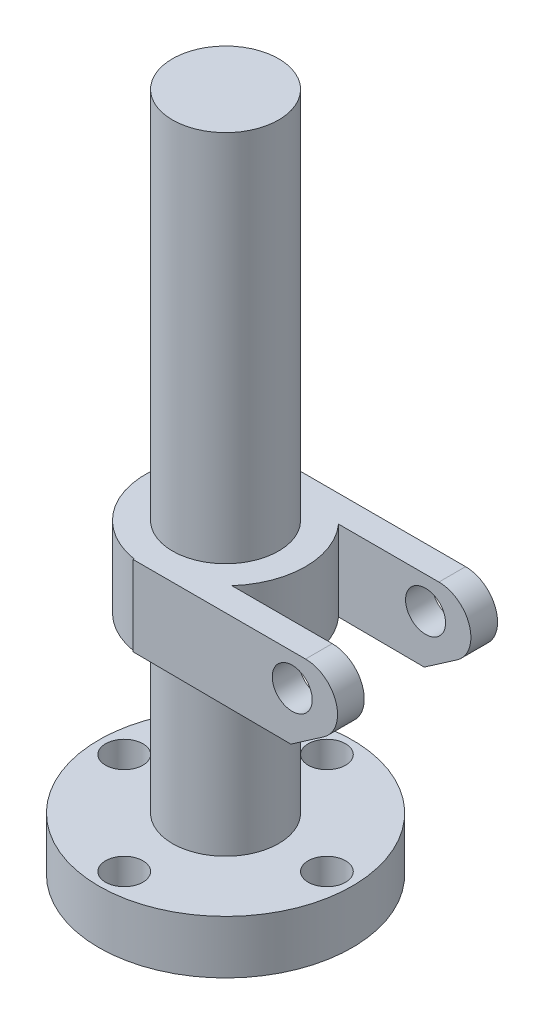
SolidWorks part; units mm, degrees
ref_plane "Front Plane" through (0, 0, 0) normal (0, 0, 1) x (1, 0, 0)
ref_plane "Top Plane" through (0, 0, 0) normal (0, 1, 0) x (1, 0, 0)
ref_plane "Right Plane" through (0, 0, 0) normal (1, 0, 0) x (0, 0, -1)
sketch "Sketch1" plane through (0, 0, 0) normal (0, 1, 0) x (1, 0, 0)
  circle A0 centre (0, 0) radius 47.5
  dimension "D1" = 95
extrude "Boss-Extrude1" add sketch "Sketch1" along normal blind 20
sketch "Sketch2" plane through (0, 20, 0) normal (0, 1, 0) x (1, 0, 0)
  circle A0 centre (0, 0) radius 19.9
  dimension "D1" = 39.8
extrude "Boss-Extrude2" add sketch "Sketch2" along normal blind 65
sketch "Sketch3" plane through (0, 85, 0) normal (0, 1, 0) x (1, 0, 0)
  circle A0 centre (0, 0) radius 30
  dimension "D1" = 60
extrude "Boss-Extrude3" add sketch "Sketch3" along normal blind 30
sketch "Sketch4" plane through (0, 115, 0) normal (0, 1, 0) x (1, 0, 0)
  circle A0 centre (0, 0) radius 19.9
  dimension "D1" = 39.8
extrude "Boss-Extrude4" add sketch "Sketch4" along normal blind 140
sketch "Sketch5" plane through (0, 0, 0) normal (0, 0, 1) x (1, 0, 0)
  line L0 (-4.6849, 115) -> (60, 115)
  line L1 (30, 115) -> (-30, 115) construction
  line L3 (66.8202, 93.1265) -> (54.4856, 84.6063)
  line L4 (54.4856, 84.6063) -> (-4.6849, 85)
  line L5 (-30, 85) -> (30, 85) construction
  line L6 (-4.6849, 85) -> (-4.6849, 115)
  arc A0 (66.8202, 93.1265) -> (60, 115) centre (60, 103) ccw
  dimension "D1" = 24
  dimension "D2" = 60
extrude "Boss-Extrude5" add sketch "Sketch5" along normal blind 30 and the other way blind 30
sketch "Sketch6" plane through (0, 115, 0) normal (0, 1, 0) x (1, 0, 0)
  line L0 (85.6132, 20) -> (85.6132, -20)
  line L1 (85.6132, -20) -> (22.3607, -20)
  line L3 (22.3607, 20) -> (85.6132, 20)
  line L4 (60, 30) -> (-4.6849, 30) construction
  line L5 (60, -30) -> (-4.6849, -30) construction
  arc A0 (22.3607, -20) -> (22.3607, 20) centre (0, 0) ccw
  dimension "D1" = 60
  dimension "D2" = 10
  dimension "D3" = 10
extrude "Cut-Extrude1" cut sketch "Sketch6" against normal blind 40
sketch "Sketch7" plane through (0, 0, 30) normal (0, 0, 1) x (1, 0, 0)
  line L0 (60, 115) -> (-4.6849, 115) construction
  circle A0 centre (55, 103) radius 7.5
  dimension "D1" = 15
  dimension "D2" = 12
  dimension "D3" = 55
extrude "Cut-Extrude2" cut sketch "Sketch7" against normal through all
sketch "Sketch8" plane through (0, 0, 0) normal (0, -1, 0) x (1, 0, 0)
  circle A0 centre (0, 0) radius 20
  dimension "D1" = 40
extrude "Cut-Extrude3" cut sketch "Sketch8" against normal blind 15
sketch "Sketch9" plane through (0, 20, 0) normal (0, 1, 0) x (1, 0, 0)
  circle A0 centre (0, 0) radius 38 construction
  point P0 (0, 38)
  point P5 (0, 0)
  point P6 (0, 0)
  dimension "D1" = 76
sketch "Sketch11" plane through (0, 20, 0) normal (0, 1, 0) x (1, 0, 0)
  point P0 (0, 38)
sketch "Sketch13" plane through (0, 20, 0) normal (0, 1, 0) x (1, 0, 0)
sketch "Sketch15" plane through (0, 20, 0) normal (0, 1, 0) x (1, 0, 0)
  point P0 (0, 38)
hole_wizard "CBORE for M5 Hex Head Bolt3" positions "Sketch15" profile "Sketch14" counterbore size "M5" standard "ISO" end condition through all
sketch "Sketch14" plane through (0, 20, -38) normal (1, 0, 0) x (0, 0, 1)
  line L0 (0, 0) -> (0, 20)
  line L1 (0, 20) -> (5, 20)
  line L3 (5, 20) -> (5, 10)
  line L4 (5, 10) -> (7, 10)
  line L5 (7, 10) -> (7, 0)
  line L7 (7, 0) -> (0, 0)
  line L11 (0, -6.35) -> (0, 107.95) construction
  dimension "Thru Hole Dia." = 10
  dimension "Thru Hole Depth" = 20
  dimension "C'Bore Dia." = 14
  dimension "C'Bore Depth" = 10
pattern_circular "CirPattern1" count 4 over 360 about axis through (0, 20, 0) along (0, 1, 0) of "CBORE for M5 Hex Head Bolt3"
